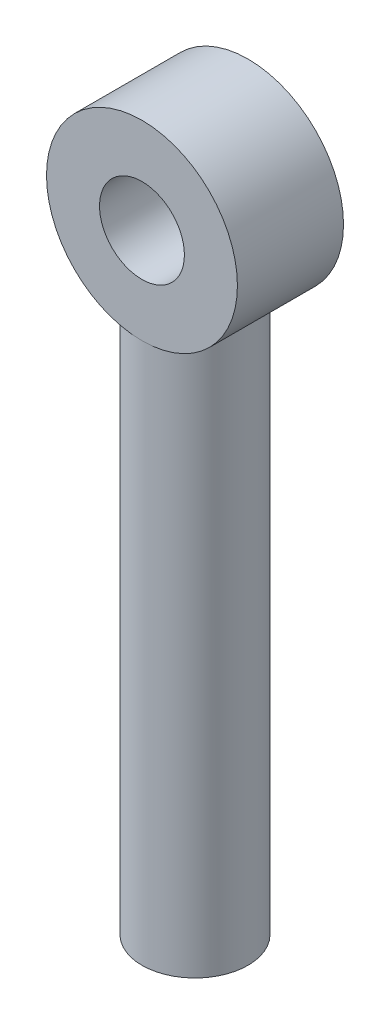
SolidWorks part; units mm, degrees
ref_plane "前视基准面" through (0, 0, 0) normal (0, 0, 1) x (1, 0, 0)
ref_plane "上视基准面" through (0, 0, 0) normal (0, 1, 0) x (1, 0, 0)
ref_plane "右视基准面" through (0, 0, 0) normal (1, 0, 0) x (0, 0, -1)
ref_plane "基准面4" through (0, -20, 0) normal (0, -1, 0) x (1, 0, 0)
sketch "草图1" plane through (0, -20, 0) normal (0, -1, 0) x (1, 0, 0)
  line L0 (13.5, -23.5) -> (9, -23.5)
  line L1 (9, -23.5) -> (9, -28.5)
  line L2 (9, -28.5) -> (13.5, -28.5)
  line L3 (13.5, -28.5) -> (13.5, -23.5)
  line L4 (9, -23.5) -> (9, -28.5) construction
revolve "旋转1" add sketch "草图1" angle 360 about L4 reverse direction yes
ref_plane "基准面5" through (9, 0, 0) normal (1, 0, 0) x (0, 0, -1)
sketch "草图2" plane through (9, 0, 0) normal (1, 0, 0) x (0, 0, -1)
  line L0 (26, -23.7417) -> (23.5, -23.7417)
  line L1 (23.5, -23.7417) -> (23.5, -50)
  line L2 (23.5, -50) -> (26, -50)
  line L3 (26, -50) -> (26, -23.7417)
  line L4 (26, -50) -> (26, -23.7417) construction
revolve "旋转2" add sketch "草图2" angle 360 about L4 reverse direction yes
hole_wizard "Ø4.0 (4) 直径孔1" positions "草图4" profile "草图3" hole size "Ø4.0" standard "ANSI Metric"
sketch "草图4" plane through (0, 0, -23.5) normal (0, 0, 1) x (1, 0, 0)
  point P0 (9, -20)
sketch "草图3" plane through (9, -20, -23.5) normal (1, 0, 0) x (0, -1, 0)
  line L0 (0, 0) -> (0, 5)
  line L1 (0, 5) -> (2, 5)
  line L2 (2, 5) -> (2, 0)
  line L5 (2, 0) -> (0, 0)
  line L11 (0, -6.35) -> (0, 107.95) construction
  dimension "通孔孔直径" = 4
  dimension "通孔孔深度" = 5
